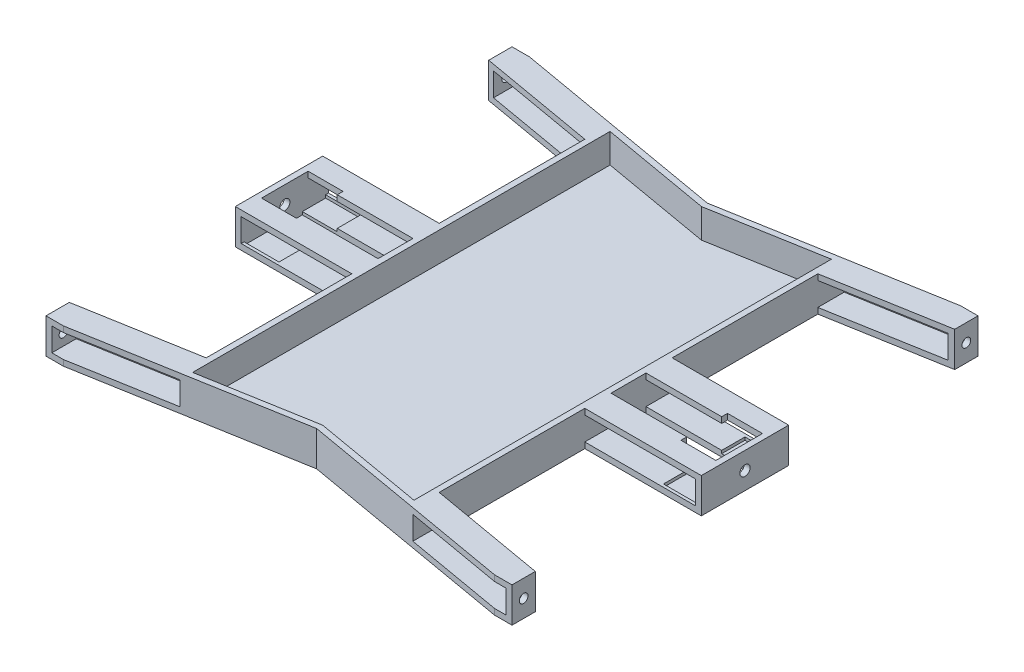
SolidWorks part; units mm, degrees
ref_plane "Front Plane" through (0, 0, 0) normal (0, 0, 1) x (1, 0, 0)
ref_plane "Top Plane" through (0, 0, 0) normal (0, 1, 0) x (1, 0, 0)
ref_plane "Right Plane" through (0, 0, 0) normal (1, 0, 0) x (0, 0, -1)
sketch "Sketch1" plane through (0, 0, 0) normal (0, 1, 0) x (1, 0, 0)
  line L1 (-55, 0) -> (55, 0) construction
  line L2 (80, 15) -> (80, -15)
  line L3 (80, -15) -> (40, -15)
  line L4 (40, -15) -> (40, -65)
  line L5 (40, -65) -> (80, -72)
  line L6 (80, -72) -> (80, -80)
  line L7 (80, -80) -> (74, -80)
  line L8 (74, -80) -> (0, -67.05)
  line L9 (0, -55) -> (0, 55) construction
  line L11 (-80, 15) -> (-80, -15)
  line L12 (-80, -15) -> (-40, -15)
  line L13 (-40, -15) -> (-40, -65)
  line L14 (-40, -65) -> (-80, -72)
  line L15 (-80, -72) -> (-80, -80)
  line L16 (-80, -80) -> (-74, -80)
  line L17 (-74, -80) -> (0, -67.05)
  line L18 (80, 15) -> (40, 15)
  line L19 (40, 15) -> (40, 65)
  line L20 (80, 80) -> (74, 80)
  line L21 (80, 72) -> (80, 80)
  line L22 (40, 65) -> (80, 72)
  line L23 (74, 80) -> (0, 67.05)
  line L24 (-80, 72) -> (-80, 80)
  line L25 (-80, 80) -> (-74, 80)
  line L26 (-74, 80) -> (0, 67.05)
  line L27 (-40, 65) -> (-80, 72)
  line L28 (-80, 15) -> (-40, 15)
  line L29 (-40, 15) -> (-40, 65)
  point P21 (80, 0)
  point P33 (-80, 0)
  dimension "D3" = 15
  dimension "D5" = 8
  dimension "D6" = 50
  dimension "D8" = 6
  dimension "D1" = 80
  dimension "D2" = 80
  dimension "D4" = 80
  dimension "D7" = 40
extrude "Boss-Extrude1" add sketch "Sketch1" along normal blind 6 and the other way blind 6
sketch "Sketch2" plane through (0, 0, 80) normal (0, 0, 1) x (1, 0, 0)
  line L1 (-78, -4) -> (78, -4)
  line L2 (-78, -4) -> (-78, 4)
  line L3 (-78, 4) -> (78, 4)
  line L4 (78, -4) -> (78, 4)
  line L7 (55, 0) -> (-55, 0) construction
  dimension "D1" = 4
  dimension "D2" = 4
  dimension "D3" = 78
  dimension "D4" = 78
extrude "Cut-Extrude1" cut sketch "Sketch2" against normal blind 160
sketch "Sketch4" plane through (0, 6, 0) normal (0, 1, 0) x (1, 0, 0)
  line L0 (-6.6, 0) -> (6.6, 0) construction
  line L1 (-78, 6) -> (-40, 6)
  line L2 (-78, 6) -> (-78, -6)
  line L3 (-78, -6) -> (-40, -6)
  line L4 (-40, 6) -> (-40, -6)
  line L5 (-80, 15) -> (-80, -15) construction
  line L6 (-40, -15) -> (-40, -65) construction
  line L7 (0, -6.6) -> (0, 6.6) construction
  line L8 (78, -6) -> (40, -6)
  line L9 (40, 6) -> (40, -6)
  line L10 (78, 6) -> (40, 6)
  line L11 (78, 6) -> (78, -6)
  dimension "D1" = 6
  dimension "D2" = 6
  dimension "D3" = 2
extrude "Cut-Extrude2" cut sketch "Sketch4" against normal blind 12
sketch "Sketch6" plane through (0, 0, 0) normal (1, 0, 0) x (0, 0, -1)
  line L0 (-72, 0) -> (-80, 0) construction
  line L1 (72, 0) -> (80, 0) construction
  circle A0 centre (-76, 0) radius 1.5
  circle A1 centre (76, 0) radius 1.5
  point P6 (-76, 0)
  point P10 (76, 0)
  dimension "D1" = 3
extrude "Cut-Extrude3" cut sketch "Sketch6" against normal through all both and the other way through all
sketch "Sketch7" plane through (80, 0, 0) normal (1, 0, 0) x (0, 0, -1)
  circle A0 centre (0, 0) radius 1.75
  dimension "D1" = 3.5
extrude "Cut-Extrude4" cut sketch "Sketch7" against normal up to surface (160 mm away) up to face at (-80, 0, 0)
sketch "Sketch8" plane through (0, 6, 0) normal (0, 1, 0) x (1, 0, 0)
  line L0 (0, 67.05) -> (0, -67.05) construction
  line L1 (78, -6) -> (78, 6) construction
  line L2 (78, 8) -> (66, 8)
  line L3 (78, 8) -> (78, -8)
  line L4 (78, -8) -> (66, -8)
  line L5 (66, 8) -> (66, -8)
  line L6 (-78, 0) -> (80, 0) construction
  line L7 (-78, 6) -> (-78, -6) construction
  line L8 (80, -15) -> (80, 15) construction
  line L9 (-78, -8) -> (-66, -8)
  line L10 (-66, 8) -> (-66, -8)
  line L11 (-78, 8) -> (-66, 8)
  line L12 (-78, 8) -> (-78, -8)
  point P16 (66, 0)
  dimension "D1" = 16
  dimension "D2" = 12
extrude "Cut-Extrude5" cut sketch "Sketch8" against normal up to surface (2 mm away) up to face at (0, 4, 0)
sketch "Sketch9" plane through (0, -4, 0) normal (0, 1, 0) x (1, 0, 0)
  line L0 (78, -6) -> (78, -15) construction
  line L1 (78, -15) -> (65, -15) construction
  line L2 (78, -15) -> (78, 15) construction
  line L3 (78, 15) -> (65, 15) construction
  line L4 (65, -15) -> (65, 15) construction
  line L6 (78, -14) -> (66, -14)
  line L7 (66, -14) -> (66, 14)
  line L8 (78, 14) -> (66, 14)
  line L9 (78, 14) -> (78, -14)
  line L11 (0, -6.6) -> (0, 6.6) construction
  line L12 (-78, 14) -> (-66, 14)
  line L13 (-78, 14) -> (-78, -14)
  line L14 (-66, -14) -> (-66, 14)
  line L15 (-78, -14) -> (-66, -14)
  line L16 (40, -15) -> (78, -15) construction
  line L17 (78, 15) -> (40, 15) construction
  dimension "D2" = 13
  dimension "D1" = 1
extrude "Cut-Extrude6" cut sketch "Sketch9" against normal blind 1
sketch "Sketch11" plane through (0, 6, 0) normal (0, 1, 0) x (1, 0, 0)
  line L0 (-40, -74.05) -> (-40, 74.05)
  line L1 (-74, -80) -> (0, -67.05) construction
  line L2 (0, 67.05) -> (-74, 80) construction
  line L3 (40, 74.05) -> (40, -74.05)
  line L4 (74, 80) -> (0, 67.05) construction
  line L5 (0, -67.05) -> (74, -80) construction
  line L6 (40, 15) -> (40, 65) construction
  line L7 (-40, 65) -> (-40, 15) construction
  line L8 (0, -67.05) -> (40, -74.05)
  line L9 (-40, -74.05) -> (0, -67.05)
  line L10 (0, 67.05) -> (-40, 74.05)
  line L11 (40, 74.05) -> (0, 67.05)
extrude "Cut-Extrude7" cut sketch "Sketch11" against normal up to surface (2 mm away) up to face at (0, 4, 0)
sketch "Sketch12" plane through (0, -4, 0) normal (0, 1, 0) x (1, 0, 0)
  line L0 (-40, 74.05) -> (-40, -74.05)
  line L1 (-74, -80) -> (0, -67.05) construction
  line L2 (40, 74.05) -> (40, -74.05)
  line L3 (-40, -74.05) -> (0, -67.05)
  line L4 (0, -67.05) -> (40, -74.05)
  line L5 (-40, 74.05) -> (0, 67.05)
  line L6 (0, 67.05) -> (40, 74.05)
  line L7 (0, 65.0196) -> (38, 71.6696)
  line L8 (38, 71.6696) -> (38, -71.6696)
  line L9 (0, -65.0196) -> (38, -71.6696)
  line L10 (-38, -71.6696) -> (0, -65.0196)
  line L11 (-38, 71.6696) -> (-38, -71.6696)
  line L12 (-38, 71.6696) -> (0, 65.0196)
  dimension "D1" = 2
extrude "Boss-Extrude2" add sketch "Sketch12" along normal blind 10
equation "\"A\"=2"
equation "\"D5@Sketch1\"=4*\"A\""
equation "\"D8@Sketch1\"=3*\"A\""
equation "\"D2@Sketch1\"=40*\"A\""
equation "\"D4@Sketch1\"=40*\"A\""
equation "\"D7@Sketch1\"=20*\"A\""
equation "\"D1@Boss-Extrude1\"=3*\"A\""
equation "\"D2@Boss-Extrude1\"=3*\"A\""
equation "\"D1@Sketch2\"=2*\"A\""
equation "\"D2@Sketch2\"=2*\"A\""
equation "\"D1@Sketch4\"=3*\"A\""
equation "\"D2@Sketch4\"=3*\"A\""
equation "\"D3@Sketch4\"=\"A\""
equation "\"D1@Cut-Extrude2\"=6*\"A\""
equation "\"D1@Cut-Extrude1\"=80*\"A\""
equation "\"D3@Sketch1\"= 7.5 * \"A\""
equation "\"D3@Sketch2\"=\"A\" * 39"
equation "\"D4@Sketch2\"=\"A\" * 39"
